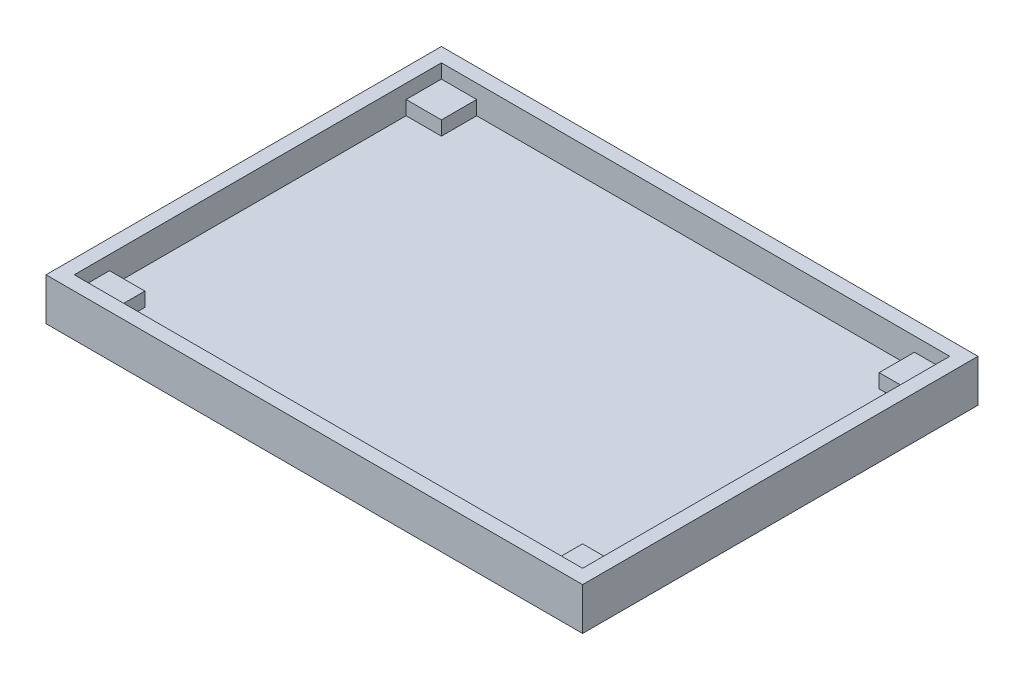
SolidWorks part; units mm, degrees
ref_plane "Front Plane" through (0, 0, 0) normal (0, 0, 1) x (1, 0, 0)
ref_plane "Top Plane" through (0, 0, 0) normal (0, 1, 0) x (1, 0, 0)
ref_plane "Right Plane" through (0, 0, 0) normal (1, 0, 0) x (0, 0, -1)
sketch "Sketch1" plane through (0, 0, 0) normal (0, 1, 0) x (1, 0, 0)
  line L0 (-1, 51) -> (71, 51)
  line L6 (-1, -1) -> (4, -1)
  line L7 (71, -1) -> (71, 51)
  line L8 (-1, -1) -> (71, -1)
  line L9 (-1, -1) -> (-1, 51)
  line L10 (-1, -1) -> (-1, 4)
  line L11 (-1, 4) -> (4, 4)
  line L12 (4, -1) -> (4, 4)
  line L13 (-1, -1) -> (4, 4) construction
  line L14 (-1, 4) -> (4, -1) construction
  line L15 (71, -1) -> (66, -1)
  line L16 (71, -1) -> (71, 4)
  line L17 (71, 4) -> (66, 4)
  line L18 (66, -1) -> (66, 4)
  line L19 (71, -1) -> (66, 4) construction
  line L20 (71, 4) -> (66, -1) construction
  line L21 (-1, 51) -> (4, 51)
  line L22 (-1, 51) -> (-1, 46)
  line L23 (-1, 46) -> (4, 46)
  line L24 (4, 51) -> (4, 46)
  line L25 (-1, 51) -> (4, 46) construction
  line L26 (-1, 46) -> (4, 51) construction
  line L27 (71, 51) -> (66, 51)
  line L28 (71, 51) -> (71, 46)
  line L29 (71, 46) -> (66, 46)
  line L30 (66, 51) -> (66, 46)
  line L31 (71, 51) -> (66, 46) construction
  line L32 (71, 46) -> (66, 51) construction
  line L33 (-1, 51) -> (-3, 51)
  line L34 (-1, 51) -> (-1, 53)
  line L35 (-1, 53) -> (-3, 53)
  line L36 (-3, 51) -> (-3, 53)
  line L37 (-1, 51) -> (-3, 53) construction
  line L38 (-1, 53) -> (-3, 51) construction
  line L39 (-3, 53) -> (73, 53)
  line L40 (-3, 53) -> (-3, -3)
  line L41 (-3, -3) -> (73, -3)
  line L42 (73, 53) -> (73, -3)
  line L43 (-3, 53) -> (73, -3) construction
  line L44 (-3, -3) -> (73, 53) construction
  point P3 (1.5, 1.5)
  point P4 (35, 25)
  point P12 (68.5, 1.5)
  point P16 (1.5, 48.5)
  point P20 (68.5, 48.5)
  point P24 (-2, 52)
  point P28 (35, 25)
  dimension "D1" = 5
  dimension "D2" = 5
  dimension "D3" = 5
  dimension "D4" = 5
  dimension "D5" = 2
  dimension "D6" = 56
  dimension "D7" = 76
extrude "Boss-Extrude1" add sketch "Sketch1" along normal blind 2 contours L30 L0 L24 L23 L9 L11 L12 L8 L18 L17 L7 L29 | L18 L8 L7 L17 | L42 L39 L34 L0 L7 L8 L6 L9 L33 L40 L41 | L0 L30 L29 L7 | L6 L12 L11 L9 | L24 L0 L9 L23 | L36 L33 L34 L35 region at (1.5, 0, -48.5) region at (-0.056, 0, -52) region at (-2, 0, -52) region at (35, 0, -25) region at (68.5, 0, -48.5) region at (1.5, 0, -1.5) region at (68.5, 0, -1.5)
extrude "Boss-Extrude2" add sketch "Sketch1<4>" along normal blind 4 contours L6 L12 L11 L9 | L24 L0 L9 L23 | L0 L30 L29 L7 | L18 L8 L7 L17 region at (1.5, 0, -48.5) region at (68.5, 0, -48.5) region at (1.5, 0, -1.5) region at (68.5, 0, -1.5)
sketch "Sketch1<4>" plane through (0, 0, 0) normal (0, 1, 0) x (1, 0, 0) same geometry as "Sketch1"
extrude "Boss-Extrude3" add sketch "Sketch1<5>" along normal blind 6 contours L42 L39 L34 L0 L7 L8 L6 L9 L33 L40 L41 | L36 L33 L34 L35 region at (-0.056, 0, -52) region at (-2, 0, -52)
sketch "Sketch1<5>" plane through (0, 0, 0) normal (0, 1, 0) x (1, 0, 0) same geometry as "Sketch1"
